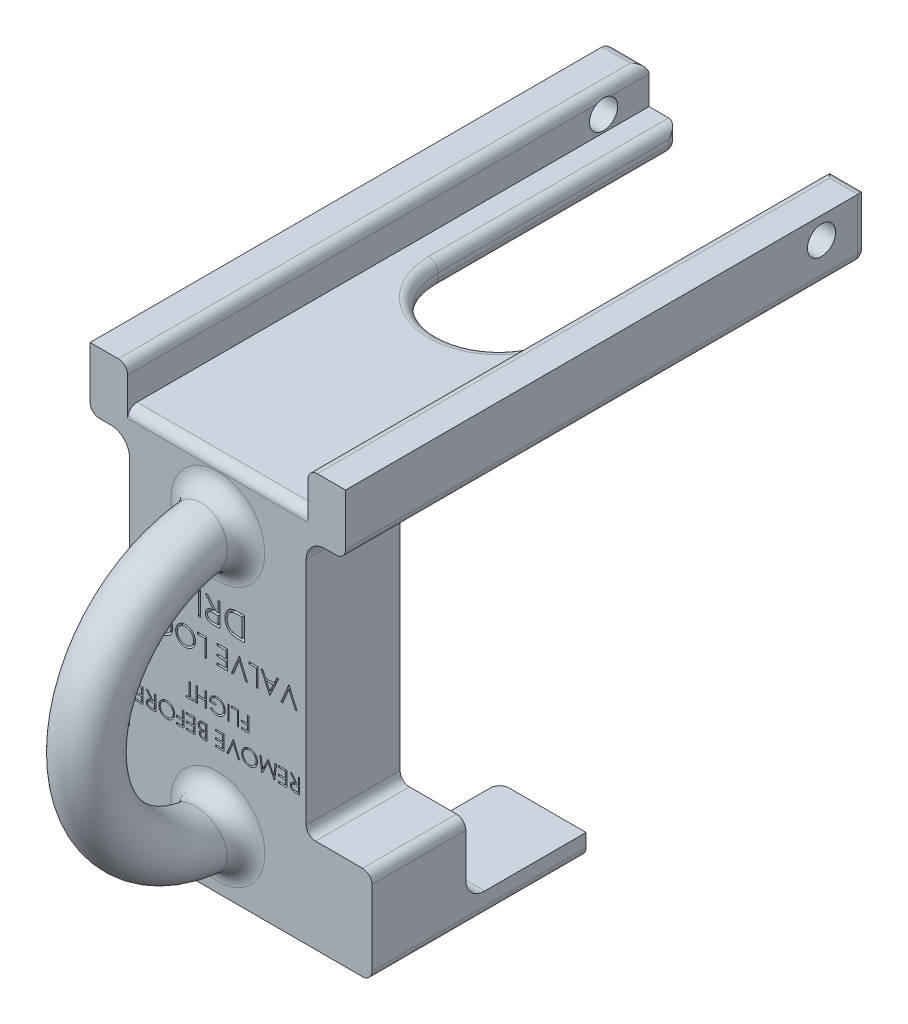
SolidWorks part; units mm, degrees
material "ABS PC"
ref_plane "Front Plane" through (0, 0, 0) normal (0, 0, 1) x (1, 0, 0)
ref_plane "Top Plane" through (0, 0, 0) normal (0, 1, 0) x (1, 0, 0)
ref_plane "Right Plane" through (0, 0, 0) normal (1, 0, 0) x (0, 0, -1)
sketch "Sketch1" plane through (0, 0, 0) normal (0, 0, 1) x (1, 0, 0)
  line L0 (0, 2.5) -> (0, -2.54) construction
  line L1 (-11.938, -2.54) -> (11.938, -2.54)
  line L2 (-11.938, -2.54) -> (-11.938, 2.5)
  line L3 (-11.938, 2.5) -> (11.938, 2.5)
  line L4 (11.938, -2.54) -> (11.938, 2.5)
  circle A0 centre (0, 0) radius 1.5
  dimension "D1" = 3
  dimension "D2" = 23.876
  dimension "D3" = 2.54
  dimension "D4" = 2.5
extrude "Boss-Extrude2" add sketch "Sketch1" along normal blind 25.4 contours L0 L3 L2 L1 A0 | L0 A0 | A0 L0 | L3 L0 A0 L1 L4 region at (6.3018, -0.0212, 0) region at (-6.3018, -0.0212, 0) region at (0.6366, 0, 0) region at (-0.6366, 0, 0)
ref_plane "Plane1" through (0, -0.02, 0) normal (0, 1, 0) x (1, 0, 0)
sketch "Sketch15" plane through (0, 2.5, 0) normal (0, 1, 0) x (1, 0, 0)
  line L0 (-11.938, 0) -> (11.938, 0) construction
  line L1 (-11.938, 0) -> (11.938, 0)
  line L3 (-11.938, 0) -> (11.938, 0)
  line L7 (-8.255, 12.61) -> (8.255, 12.61) construction
  line L10 (-11.938, 0) -> (-11.938, 45.085)
  line L11 (-11.938, 45.085) -> (-8.255, 45.085)
  line L12 (-8.255, 12.61) -> (-8.255, 45.085)
  line L14 (8.255, 12.61) -> (8.255, 45.085)
  line L15 (8.255, 45.085) -> (11.938, 45.085)
  line L16 (11.938, 0) -> (11.938, 45.085)
  arc A0 (-8.255, 12.61) -> (8.255, 12.61) centre (0, 12.61) ccw
  line M5 (11.938, 0) -> (-11.938, 0)
  dimension "D2" = 8.255
  dimension "D1" = 45.085
  dimension "D3" = 12.61
extrude "Boss-Extrude3" add sketch "Sketch15" against normal blind 3.175 contours A0 M5 region at (-11.4278, 2.5, -22.5425)
sketch "Sketch19" plane through (0, -2.54, 0) normal (0, 1, 0) x (1, 0, 0)
  line L0 (-9.144, -20.32) -> (9.144, -20.32)
  line L1 (-11.938, -25.4) -> (11.938, -25.4) construction
  line L2 (-9.144, -20.32) -> (-9.144, -12.7)
  line L3 (-9.144, -12.7) -> (-11.938, -12.7)
  line L4 (-11.938, -25.4) -> (-11.938, 45.085) construction
  line L5 (-11.938, -12.7) -> (-11.938, -25.4)
  line L6 (-11.938, -25.4) -> (11.938, -25.4)
  line L7 (11.938, -25.4) -> (11.938, -12.7)
  line L8 (11.938, -25.4) -> (11.938, 45.085) construction
  line L9 (11.938, -12.7) -> (9.144, -12.7)
  line L10 (9.144, -12.7) -> (9.144, -20.32)
  point P10 (0, -20.32)
  point P17 (0, -25.4)
  dimension "D1" = 5.08
  dimension "D2" = 18.288
  dimension "D3" = 12.7
extrude "Boss-Extrude4" add sketch "Sketch19" against normal blind 45.72
fillet "Fillet1" radius 2.54 2 edges at (9.144, -25.4, 20.32) (-9.144, -25.4, 20.32)
fillet "Fillet2" radius 2.54 2 edges at (-10.541, -2.54, 12.7) (10.541, -2.54, 12.7)
fillet "Fillet3" radius 2.54 5 edges at (9.144, -2.54, 13.97) (8.4001, -2.54, 19.5761) (0, -2.54, 20.32) (-8.4001, -2.54, 19.5761) (-9.144, -2.54, 13.97)
sketch "Sketch21" plane through (0, 0, 12.7) normal (0, 0, -1) x (-1, 0, 0)
  line L0 (11.938, -48.26) -> (11.938, -5.08) construction
  line L1 (9.144, -48.26) -> (11.938, -48.26)
  line L2 (9.144, -48.26) -> (9.144, -45.212)
  line L3 (9.144, -45.212) -> (11.938, -45.212)
  line L4 (11.938, -48.26) -> (11.938, -45.212)
  line L5 (-11.938, -48.26) -> (-11.938, -5.08) construction
  line L6 (-9.144, -48.26) -> (-11.938, -48.26)
  line L7 (-9.144, -48.26) -> (-9.144, -45.212)
  line L8 (-9.144, -45.212) -> (-11.938, -45.212)
  line L9 (-11.938, -48.26) -> (-11.938, -45.212)
  dimension "D1" = 3.048
extrude "Boss-Extrude5" add sketch "Sketch21" along normal blind 16.256
fillet "Fillet4" radius 2.54 2 edges at (-10.541, -45.212, 12.7) (10.541, -45.212, 12.7)
sketch "Sketch29" plane through (0, 0, 25.4) normal (0, 0, 1) x (1, 0, 0)
  line L0 (11.938, -29.21) -> (-11.938, -29.21) construction
  line L1 (11.938, -48.26) -> (11.938, 2.5) construction
  line L2 (-11.938, -48.26) -> (-11.938, 2.5) construction
  line L3 (11.938, -19.05) -> (-11.938, -19.05) construction
  line L4 (11.938, -25.4) -> (-11.938, -25.4) construction
  line L5 (11.938, -13.97) -> (-11.938, -13.97) construction
  line L6 (-11.938, -48.26) -> (11.938, -48.26) construction
  text T0 "REMOVE BEFORE" font "Century Gothic" height 2.032
  text T1 "FLIGHT" font "Century Gothic" height 2.032
  text T2 "VALVE LOCK" font "Century Gothic" height 2.54
  text T3 "DRL"
  dimension "D1" = 3.81
  dimension "D2" = 19.05
  dimension "D3" = 6.35
  dimension "D4" = 5.08
extrude "Cut-Extrude2" cut sketch "Sketch29" against normal blind 2.54
sketch "Sketch2" plane through (0, -25.38, 0) normal (1, 0, 0) x (0, -1, 0)
  line L1 (22.88, -25.4) -> (-27.88, -25.4) construction
  line L2 (22.88, -25.4) -> (-27.88, -25.4) construction
  arc A0 (-20.28, -25.4) -> (15.28, -25.4) centre (-2.5, -25.4) ccw
  dimension "D1" = 17.78
sweep "Sweep1" add path "Sketch2" circular profile diameter 7.62 parameters "D3"=7.62
fillet "Fillet6" radius 2.54 2 edges at (3.81, -40.66, 25.4) (3.81, -5.1, 25.4)
sketch "Sketch42" plane through (11.938, 0, 0) normal (1, 0, 0) x (0, 0, -1)
  line L0 (-25.4, -35.56) -> (-12.7, -35.56)
  line L10 (0, -2.54) -> (0, -0.675)
  line L11 (0, -0.675) -> (45.085, -0.675)
  line L12 (45.085, -0.675) -> (45.085, 2.5)
  line L13 (45.085, 2.5) -> (-25.4, 2.5)
  line L14 (-25.4, 2.5) -> (-25.4, -48.26)
  line L15 (-25.4, -48.26) -> (3.556, -48.26)
  line L16 (3.556, -48.26) -> (3.556, -45.212)
  line L17 (3.556, -45.212) -> (-10.16, -45.212)
  line L18 (-12.7, -42.672) -> (-12.7, -5.08)
  line L19 (-10.16, -2.54) -> (0, -2.54)
  line L24 (-25.4, -35.56) -> (-25.4, -48.26)
  line L25 (-25.4, -48.26) -> (3.556, -48.26)
  line L26 (3.556, -48.26) -> (3.556, -45.212)
  line L27 (3.556, -45.212) -> (-10.16, -45.212)
  line L28 (-12.7, -42.672) -> (-12.7, -35.56)
  arc A2 (-12.7, -42.672) -> (-10.16, -45.212) centre (-10.16, -42.672) ccw
  arc A3 (-10.16, -2.54) -> (-12.7, -5.08) centre (-10.16, -5.08) ccw
  arc A4 (-12.7, -42.672) -> (-10.16, -45.212) centre (-10.16, -42.672) ccw
  dimension "D2" = 12.7
  dimension "D1" = 0
extrude "Boss-Extrude6" add sketch "Sketch42" along normal blind 8.89
mirror "Mirror1" about plane through (0, 0, 0) normal (1, 0, 0) of "Boss-Extrude6"
fillet "Fillet7" radius 1.27 13 edges at (11.938, -35.56, 19.05) (-11.938, -35.56, 19.05) (-20.828, -35.56, 19.05) (20.828, -35.56, 19.05) (-20.828, -48.26, 10.922) (20.828, -48.26, 10.922) (9.144, -48.26, 7.112) (8.4001, -48.26, 19.5761) (-9.144, -48.26, 7.112) (-8.4001, -48.26, 19.5761) (9.144, -46.736, -3.556) (-9.144, -46.736, -3.556) (0, -48.26, 20.32)
sketch "Sketch44" plane through (0, 0, 25.4) normal (0, 0, 1) x (1, 0, 0)
  line L0 (-11.938, 2.5) -> (-12.192, 2.5)
  line L1 (-12.192, 2.5) -> (-12.192, 7.58)
  line L2 (-12.192, 7.58) -> (-17.272, 7.58)
  line L3 (-17.272, 7.58) -> (-17.272, -0.675)
  line L4 (-17.272, -0.675) -> (-11.938, -0.675)
  line L5 (-11.938, -34.29) -> (-11.938, 2.5) construction
  line L6 (-11.938, -0.675) -> (-11.938, 2.5)
  line L7 (11.938, -0.675) -> (-11.938, -0.675) construction
  line L8 (0, 0) -> (0, -46.8759) construction
  line L9 (17.272, -0.675) -> (11.938, -0.675)
  line L10 (17.272, 7.58) -> (17.272, -0.675)
  line L11 (12.192, 7.58) -> (17.272, 7.58)
  line L12 (12.192, 2.5) -> (12.192, 7.58)
  line L13 (11.938, 2.5) -> (12.192, 2.5)
  line L14 (11.938, -0.675) -> (11.938, 2.5)
  spline S0 degree 3 poles (6.3235, -41.1989) (6.3626, -40.3563) (6.341, -39.9355) (6.2167, -39.1032) (6.1156, -38.6992) (5.9072, -38.1109) (5.8282, -37.9178) (5.6508, -37.5376) (5.5522, -37.3505) (5.2334, -36.8103) (4.9885, -36.4741) (4.434, -35.8494) (4.1225, -35.5607) (3.4592, -35.0569) (3.1046, -34.8381) (2.3475, -34.47) (1.9542, -34.3255) (1.35, -34.1695) (1.1458, -34.1275) (0.7316, -34.064) (0.5209, -34.0426) (-0.1063, -34.011) (-0.5215, -34.0321) (-1.3463, -34.1579) (-1.7581, -34.2643) (-2.5394, -34.552) (-2.9136, -34.7335) (-3.4499, -35.0629) (-3.6245, -35.1824) (-3.9573, -35.4352) (-4.1167, -35.5691) (-4.5742, -35.9927) (-4.853, -36.3057) (-5.3487, -36.9855) (-5.5601, -37.3442) (-5.8246, -37.9094) (-5.9039, -38.1024) (-6.0444, -38.4977) (-6.1055, -38.7002) (-6.2575, -39.3085) (-6.3191, -39.7197) (-6.363, -40.5531) (-6.3444, -40.9772) (-6.2257, -41.8078) (-6.1249, -42.22) (-5.8492, -43.0066) (-5.6743, -43.3841) (-5.3551, -43.9262) (-5.2389, -44.103) (-4.9922, -44.4408) (-4.8612, -44.6027) (-4.4458, -45.068) (-4.1369, -45.3527) (-3.4649, -45.8579) (-3.109, -46.0738) (-2.3582, -46.434) (-1.9587, -46.579) (-1.1495, -46.7844) (-0.7383, -46.8466) (-0.1116, -46.8784) (0.1001, -46.8786) (0.5188, -46.8581) (0.7263, -46.8375) (1.3434, -46.7454) (1.7477, -46.6439) (2.5412, -46.3576) (2.917, -46.1776) (3.4508, -45.8546) (3.6237, -45.7381) (3.9591, -45.4868) (4.1221, -45.3516) (4.5846, -44.9275) (4.862, -44.6178) (5.3552, -43.945) (5.5716, -43.5791) (5.9234, -42.8242) (6.0619, -42.432) (6.2627, -41.6177) (6.3235, -41.1989) (6.3626, -40.3563) (6.341, -39.9355) knots -0.03125 -0.03125 0 0 0.03125 0.03125 0.0625 0.0625 0.078125 0.078125 0.09375 0.09375 0.125 0.125 0.15625 0.15625 0.1875 0.1875 0.21875 0.21875 0.234375 0.234375 0.25 0.25 0.28125 0.28125 0.3125 0.3125 0.34375 0.34375 0.359375 0.359375 0.375 0.375 0.40625 0.40625 0.4375 0.4375 0.453125 0.453125 0.46875 0.46875 0.5 0.5 0.53125 0.53125 0.5625 0.5625 0.59375 0.59375 0.609375 0.609375 0.625 0.625 0.65625 0.65625 0.6875 0.6875 0.71875 0.71875 0.75 0.75 0.765625 0.765625 0.78125 0.78125 0.8125 0.8125 0.84375 0.84375 0.859375 0.859375 0.875 0.875 0.90625 0.90625 0.9375 0.9375 0.96875 0.96875 1 1 1.03125 1.03125 1.0625 only from (6.3431, -40.7776) to (6.3431, -40.7776) construction
  dimension "D1" = 5.08
  dimension "D2" = 0.254
  dimension "D3" = 5.08
extrude "Boss-Extrude7" add sketch "Sketch44" against normal up to surface (70.485 mm away) up to face at (-10.0965, 0.9125, -45.085)
sketch "Sketch20" plane through (11.938, 0, 0) normal (1, 0, 0) x (0, 0, -1)
  line L0 (45.085, -2.54) -> (45.085, 2.5) construction
  line L2 (45.085, 7.58) -> (-25.4, 7.58) construction
  circle A0 centre (38.9382, 4.659) radius 1.905
  dimension "D2" = 3.81
  dimension "D1" = 6.1468
  dimension "D3" = 2.921
extrude "Cut-Extrude1" cut sketch "Sketch20" against normal through all and the other way through all
fillet "Fillet8" radius 1.27 20 edges at (8.255, 2.5, -28.8475) (0, 2.5, -4.355) (8.255, 0.9125, -45.085) (-8.255, 2.5, -28.8475) (-8.255, 0.9125, -45.085) (0, 2.5, 25.4) (-8.255, -0.675, -28.8475) (8.255, -0.675, -28.8475) (0, -0.675, -4.355) (0, -2.54, 0) (14.732, 7.58, -45.085) (-14.732, 7.58, -45.085) (-12.7635, -0.675, -45.085) (-17.272, 3.4525, -45.085) (12.7635, -0.675, -45.085) (17.272, 3.4525, -45.085) (17.272, -0.675, -9.8425) (-17.272, -0.675, -9.8425) (-12.192, 7.58, -9.8425) (12.192, 7.58, -9.8425)
fillet "Fillet9" radius 2.54 2 edges at (11.938, -0.675, 12.7) (-11.938, -0.675, 12.7)
